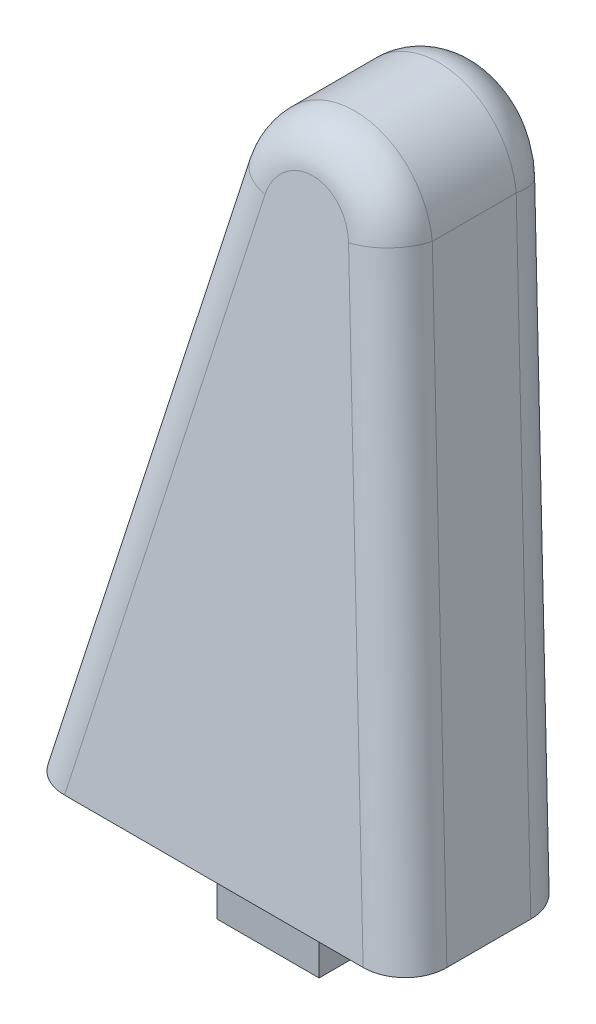
SolidWorks part; units mm, degrees
ref_plane "Front Plane" through (0, 0, 0) normal (0, 0, 1) x (1, 0, 0)
ref_plane "Top Plane" through (0, 0, 0) normal (0, 1, 0) x (1, 0, 0)
ref_plane "Right Plane" through (0, 0, 0) normal (1, 0, 0) x (0, 0, -1)
sketch "Sketch1" plane through (0, 0, 0) normal (0, 0, 1) x (1, 0, 0)
  line L0 (-52.22, 157) -> (-29.78, 157)
  line L1 (-29.78, 157) -> (-36.1008, 187.999)
  line L2 (-45.8992, 187.999) -> (-52.22, 157)
  arc A0 (-36.1008, 187.999) -> (-45.8992, 187.999) centre (-41, 187) ccw
extrude "Boss-Extrude1" add sketch "Sketch1" along normal blind 20 from offset 47
sketch "Sketch2" plane through (0, 0, 0) normal (1, 0, 0) x (0, 0, -1)
  line L0 (-67.4106, 150) -> (-81, 150)
  line L1 (-81, 150) -> (-81, 200)
  line L2 (-81, 200) -> (-58.5943, 200)
  line L3 (-58.5943, 200) -> (-67.4106, 150)
extrude "Boss-Extrude2" add sketch "Sketch2" along normal blind 30 from offset 56 separate body offset against normal yes
combine bodies "Combine1" operation type subtract main body 101 bodies to subtract 102
sketch "Sketch3" plane through (0, 0, 0) normal (1, 0, 0) x (0, 0, -1)
  line L0 (-57.4106, 150) -> (-48.5943, 200)
  line L1 (-48.5943, 200) -> (-36, 200)
  line L2 (-36, 200) -> (-36, 150)
  line L3 (-36, 150) -> (-57.4106, 150)
extrude "Boss-Extrude3" add sketch "Sketch3" along normal blind 30 from offset 56 separate body offset against normal yes
combine bodies "Combine2" operation type subtract main body 103 bodies to subtract 104
fillet "Fillet1" radius 2.5 3 edges at (-49.0596, 172.4995, 63.4434) (-41, 192, 60.0049) (-32.9404, 172.4995, 63.4434)
fillet "Fillet2" radius 2.5 3 edges at (-49.0596, 172.4995, 53.4434) (-41, 192, 50.0049) (-32.9404, 172.4995, 53.4434)
sketch "Sketch4" plane through (0, 0, 0) normal (0, 0, 1) x (1, 0, 0)
  line L1 (-44, 152) -> (-38, 152)
  line L2 (-44, 152) -> (-44, 157.01)
  line L3 (-44, 157.01) -> (-38, 157.01)
  line L4 (-38, 152) -> (-38, 157.01)
extrude "Boss-Extrude4" add sketch "Sketch4" along normal blind 4 from offset 59
sketch "Sketch5" plane through (0, 0, 0) normal (0, 1, 0) x (1, 0, 0)
  circle A0 centre (-47.5, -61) radius 1
extrude "Boss-Extrude5" add sketch "Sketch5" along normal blind 7.1 from offset 156.9 separate body
combine bodies "Combine3" operation type subtract main body 106 bodies to subtract 107
